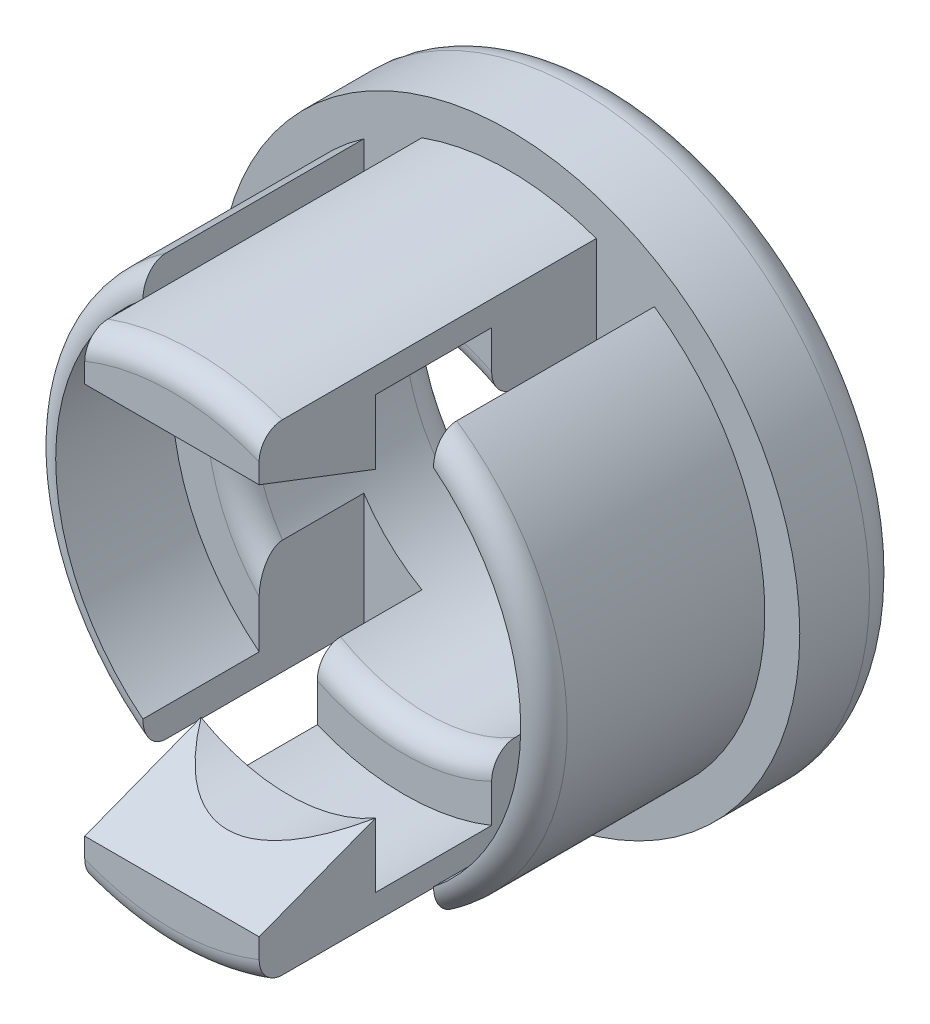
SolidWorks part; units mm, degrees
material "ABS"
ref_plane "Спереди" through (0, 0, 0) normal (0, 0, 1) x (1, 0, 0)
ref_plane "Сверху" through (0, 0, 0) normal (0, 1, 0) x (1, 0, 0)
ref_plane "Справа" through (0, 0, 0) normal (1, 0, 0) x (0, 0, -1)
sketch "Эскиз1" plane through (0, 0, 0) normal (0, 0, 1) x (1, 0, 0)
  circle A0 centre (0, 0) radius 2.5
  dimension "D1" = 5
extrude "Бобышка-Вытянуть1" add sketch "Эскиз1" along normal blind 0.9
sketch "Эскиз2" plane through (0, 0, 0.9) normal (0, 0, 1) x (1, 0, 0)
  circle A0 centre (0, 0) radius 2.2
  dimension "D1" = 4.4
extrude "Бобышка-Вытянуть2" add sketch "Эскиз2" along normal blind 2.9
sketch "Эскиз3" plane through (0, 0, 3.8) normal (0, 0, 1) x (1, 0, 0)
  circle A0 centre (0, 0) radius 1.5
  dimension "D1" = 3
extrude "Вырез-Вытянуть1" cut sketch "Эскиз3" against normal through all both and the other way through all
sketch "Эскиз4" plane through (0, 0, 3.8) normal (0, 0, 1) x (1, 0, 0)
  line L1 (-1.25, 4) -> (-0.75, 4)
  line L2 (-1.25, 4) -> (-1.25, -4)
  line L3 (-1.25, -4) -> (-0.75, -4)
  line L4 (-0.75, 4) -> (-0.75, -4)
  line L5 (1.25, 4) -> (0.75, 4)
  line L6 (1.25, 4) -> (1.25, -4)
  line L7 (1.25, -4) -> (0.75, -4)
  line L8 (0.75, 4) -> (0.75, -4)
  dimension "D1" = 0.5
  dimension "D2" = 8
  dimension "D3" = 0.75
  dimension "D4" = 4
  dimension "D5" = 0.5
  dimension "D6" = 0.75
extrude "Вырез-Вытянуть2" cut sketch "Эскиз4" against normal blind 2.9
sketch "Эскиз5" plane through (0, 0, 3.8) normal (0, 0, 1) x (1, 0, 0)
  line L1 (-1.25, 1.8104) -> (-3.25, 1.8104)
  line L2 (-1.25, 1.8104) -> (-1.25, -4.1896)
  line L3 (-1.25, -4.1896) -> (-3.25, -4.1896)
  line L4 (-3.25, 1.8104) -> (-3.25, -4.1896)
  line L5 (1.25, 1.8104) -> (3.25, 1.8104)
  line L6 (1.25, 1.8104) -> (1.25, -4.1896)
  line L7 (1.25, -4.1896) -> (3.25, -4.1896)
  line L8 (3.25, 1.8104) -> (3.25, -4.1896)
  dimension "D1" = 6
  dimension "D2" = 2
  dimension "D3" = 2
  dimension "D4" = 6
extrude "Вырез-Вытянуть3" cut sketch "Эскиз5" against normal blind 1
sketch "Эскиз6" plane through (0, 0, 2.8) normal (0, 0, 1) x (1, 0, 0)
  circle A0 centre (0, 0) radius 2
  dimension "D1" = 4
extrude "Вырез-Вытянуть4" cut sketch "Эскиз6" against normal blind 1
sketch "Эскиз7" plane through (-0.75, 0, 0) normal (-1, 0, 0) x (0, 0, 1)
  line L0 (3.8, 1.6836) -> (2.8, 1.299)
  line L1 (3.8, 1.299) -> (3.8, 2.0682) construction
  line L2 (2.8, 1.299) -> (3.8, 1.299)
  line L3 (3.8, 1.299) -> (3.8, 1.6836)
  line L4 (3.8, -1.6836) -> (2.8, -1.299)
  line L5 (3.8, -2.0682) -> (3.8, -1.299) construction
  line L6 (2.8, -1.299) -> (3.8, -1.299)
  line L7 (3.8, -1.299) -> (3.8, -1.6836)
extrude "Вырез-Вытянуть5" cut sketch "Эскиз7" against normal through all
fillet "Скругление1" radius 0.3 2 edges at (2.5, 0, 0) (1.5, 0, 0)
fillet "Скругление2" radius 0.2 8 edges at (1.5, 0, 1.8) (0, -1.5, 1.8) (0, 1.5, 1.8) (-1.5, 0, 1.8) (0, 2.2, 3.8) (0, -2.2, 3.8) (2.2, 0, 2.8) (-2.2, 0, 2.8)
